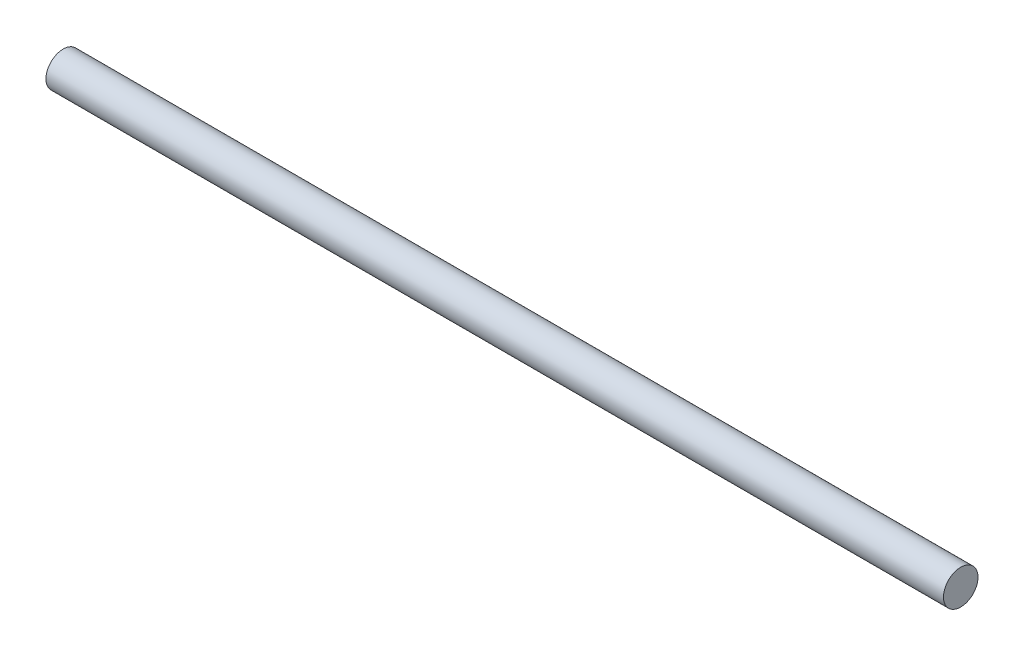
SolidWorks part; units mm, degrees
material "Cast Stainless Steel"
ref_plane "Front" through (0, 0, 0) normal (0, 0, 1) x (1, 0, 0)
ref_plane "Top" through (0, 0, 0) normal (0, 1, 0) x (1, 0, 0)
ref_plane "Right" through (0, 0, 0) normal (1, 0, 0) x (0, 0, -1)
sketch "Sketch1" plane through (0, 0, 0) normal (1, 0, 0) x (0, 0, -1)
  circle A0 centre (0, 0) radius 6.35
  dimension "D1" = 12.7
extrude "Boss-Extrude1" add sketch "Sketch1" along normal blind 330.2
